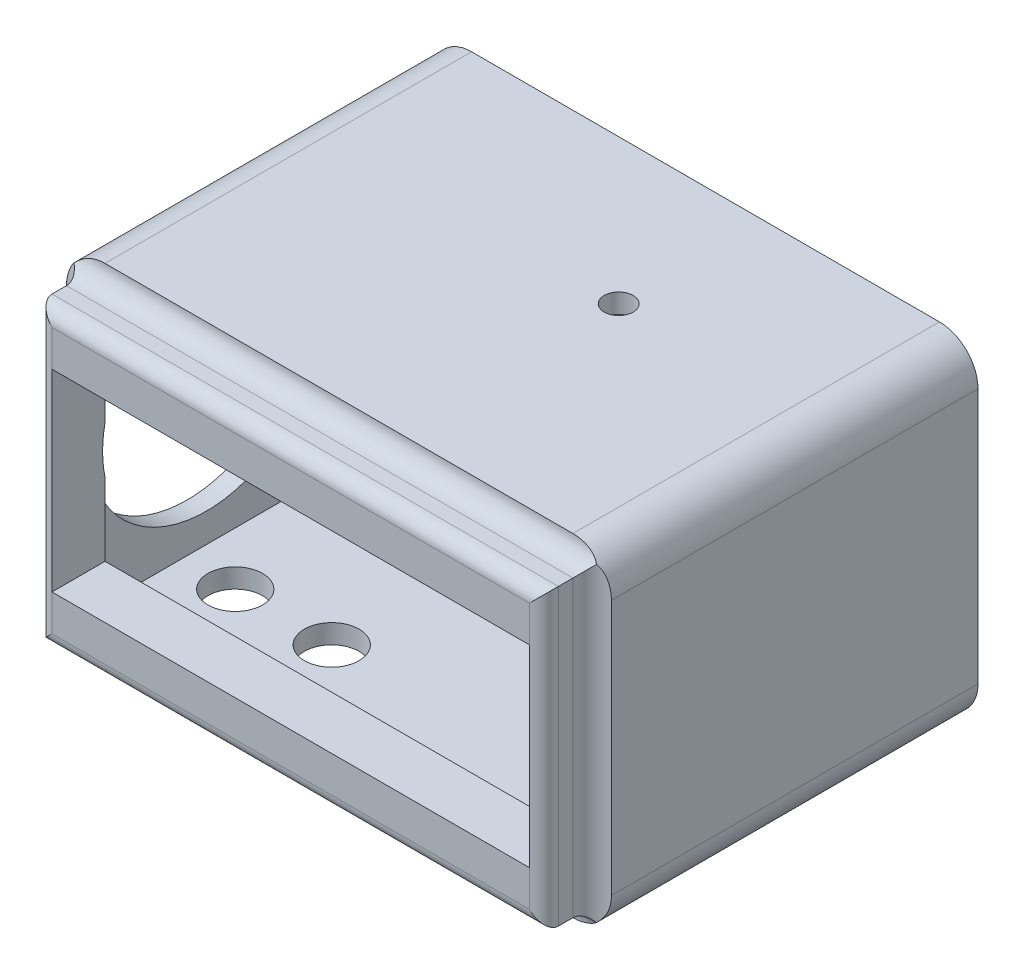
SolidWorks part; units mm, degrees
ref_plane "Ön Düzlem" through (0, 0, 0) normal (0, 0, 1) x (1, 0, 0)
ref_plane "Üst Düzlem" through (0, 0, 0) normal (0, 1, 0) x (1, 0, 0)
ref_plane "Sağ Düzlem" through (0, 0, 0) normal (1, 0, 0) x (0, 0, -1)
sketch "Çizim1" plane through (0, 0, 0) normal (0, 0, 1) x (1, 0, 0)
  line L1 (-49.5, -20) -> (49.5, -20)
  line L2 (-49.5, -20) -> (-49.5, 20)
  line L3 (-49.5, 20) -> (49.5, 20)
  line L4 (49.5, -20) -> (49.5, 20)
  line L5 (-49.5, -20) -> (49.5, 20) construction
  line L6 (-49.5, 20) -> (49.5, -20) construction
  line L7 (-52.5, -30.5) -> (52.5, -30.5)
  line L8 (-52.5, -30.5) -> (-52.5, 30.5)
  line L9 (-52.5, 30.5) -> (52.5, 30.5)
  line L10 (52.5, -30.5) -> (52.5, 30.5)
  line L11 (-52.5, -30.5) -> (52.5, 30.5) construction
  line L12 (-52.5, 30.5) -> (52.5, -30.5) construction
  point P0 (0, 0)
  point P6 (0, 0)
  dimension "D1" = 40
  dimension "D2" = 61
  dimension "D3" = 99
  dimension "D4" = 105
extrude "Yükseklik-Ekstrüzyon1" add sketch "Çizim1" along normal blind 11
sketch "Çizim2" plane through (0, 0, 0) normal (0, 0, -1) x (-1, 0, 0)
  line L1 (52.5, 30.5) -> (-52.5, 30.5)
  line L2 (52.5, 30.5) -> (52.5, -30.5)
  line L3 (52.5, -30.5) -> (-52.5, -30.5)
  line L4 (-52.5, 30.5) -> (-52.5, -30.5)
  line L5 (56.5, 34.5) -> (-56.5, 34.5)
  line L6 (56.5, 34.5) -> (56.5, -34.5)
  line L7 (56.5, -34.5) -> (-56.5, -34.5)
  line L8 (-56.5, 34.5) -> (-56.5, -34.5)
  dimension "D1" = 4
  dimension "D2" = 4
  dimension "D3" = 4
  dimension "D4" = 4
extrude "Yükseklik-Ekstrüzyon2" add sketch "Çizim2" along normal blind 70 separate body
sketch "Çizim3" plane through (0, 0, 0) normal (0, 0, 1) x (1, 0, 0)
  line L1 (-56.5, 34.5) -> (56.5, 34.5)
  line L2 (-56.5, 34.5) -> (-56.5, -34.5)
  line L3 (-56.5, -34.5) -> (56.5, -34.5)
  line L4 (56.5, 34.5) -> (56.5, -34.5)
  line L5 (49.5, -20) -> (-49.5, -20)
  line L6 (49.5, -20) -> (49.5, 20)
  line L7 (49.5, 20) -> (-49.5, 20)
  line L8 (-49.5, -20) -> (-49.5, 20)
extrude "Yükseklik-Ekstrüzyon3" add sketch "Çizim3" along normal blind 1
sketch "Çizim4" plane through (-56.5, 0, 0) normal (-1, 0, 0) x (0, 0, 1)
  line L0 (1, 0) -> (-24, 0) construction
  line L1 (1, 34.5) -> (1, -34.5) construction
  circle A0 centre (-24, 0) radius 24.5
  dimension "D2" = 49
  dimension "D1" = 25
extrude "Kes-Ekstrüzyon1" cut sketch "Çizim4" against normal blind 7
sketch "Çizim5" plane through (0, 34.5, 0) normal (0, 1, 0) x (1, 0, 0)
  line L0 (-56.5, 45) -> (9, 45) construction
  line L1 (-56.5, -1) -> (-56.5, 70) construction
  line L2 (9, 45) -> (15, 45) construction
  line L3 (15, 45) -> (56.5, 45) construction
  line L4 (56.5, -1) -> (56.5, 70) construction
  line L6 (-56.5, 70) -> (56.5, 70) construction
  circle A0 centre (12, 45) radius 3
  dimension "D1" = 6
  dimension "D2" = 65.5
  dimension "D3" = 25
extrude "Kes-Ekstrüzyon2" cut sketch "Çizim5" against normal blind 7
sketch "Çizim6" plane through (0, -34.5, 0) normal (0, -1, 0) x (-1, 0, 0)
  line L0 (56.5, -1) -> (56.5, 70) construction
  line L1 (52.5, -1) -> (-52.5, -1) construction
  line L3 (-56.5, 70) -> (56.5, 70) construction
  line L4 (-38.5, 15) -> (-49.5, 15)
  line L5 (-38.5, 15) -> (-38.5, 25)
  line L6 (-38.5, 25) -> (-49.5, 25)
  line L7 (-49.5, 15) -> (-49.5, 25)
  circle A0 centre (41.5, 19) radius 5.6662
  circle A1 centre (21.5, 19) radius 5.6662
  dimension "D1" = 15
  dimension "D20" = 20
  dimension "D3" = 20
  dimension "D4" = 10
  dimension "D5" = 11
  dimension "D6" = 95
  dimension "D7" = 45
extrude "Kes-Ekstrüzyon3" cut sketch "Çizim6" against normal blind 7
fillet "Radyus1" radius 4 4 edges at (0, -30.5, 1) (52.5, 0, 1) (-52.5, 0, 1) (0, 30.5, 1)
fillet "Radyus2" radius 3 4 edges at (0, -30.5, 11) (52.5, 0, 11) (0, 30.5, 11) (-52.5, 0, 11)
sketch "Çizim7" plane through (0, 0, -70) normal (0, 0, -1) x (-1, 0, 0)
  line L0 (52.5, -30.5) -> (52.5, 30.5) construction
  line L1 (-52.5, 30.5) -> (52.5, 30.5)
  line L2 (-52.5, 30.5) -> (-52.5, 15.5)
  line L3 (-52.5, 15.5) -> (52.5, 15.5)
  line L4 (52.5, 30.5) -> (52.5, 15.5)
  dimension "D1" = 15
sketch "Çizim8" plane through (0, 0, -70) normal (0, 0, -1) x (-1, 0, 0)
  line L0 (-47.5, 24.5) -> (-56.5, 24.5) construction
  line L1 (-47.5, 29.5) -> (47.5, 29.5)
  line L2 (-47.5, 29.5) -> (-47.5, 24.5)
  line L3 (-47.5, 24.5) -> (47.5, 24.5)
  line L4 (47.5, 29.5) -> (47.5, 24.5)
  line L5 (-56.5, 34.5) -> (-56.5, -34.5) construction
  line L6 (47.5, 24.5) -> (56.5, 24.5) construction
  line L7 (56.5, -34.5) -> (56.5, 34.5) construction
  line L8 (56.5, 34.5) -> (-56.5, 34.5) construction
  dimension "D1" = 95
  dimension "D2" = 5
  dimension "D3" = 5
fillet "Radyus4" radius 8 4 edges at (56.5, -34.5, -34.5) (-56.5, -34.5, -34.5) (56.5, 34.5, -34.5) (-56.5, 34.5, -34.5)
sketch "Çizim13" plane through (0, 0, -70) normal (0, 0, -1) x (-1, 0, 0)
  line L0 (-56.5, 26.5) -> (-56.5, -26.5) construction
  line L1 (-48.5, -34.5) -> (48.5, -34.5) construction
  line L2 (56.5, -26.5) -> (56.5, 26.5) construction
  line L3 (48.5, 34.5) -> (-48.5, 34.5) construction
  line L4 (-56.5, 26.5) -> (-56.5, -26.5)
  line L5 (-48.5, -34.5) -> (48.5, -34.5)
  line L6 (56.5, -26.5) -> (56.5, 26.5)
  line L7 (48.5, 34.5) -> (-48.5, 34.5)
  arc A0 (-56.5, -26.5) -> (-48.5, -34.5) centre (-48.5, -26.5) ccw construction
  arc A1 (48.5, -34.5) -> (56.5, -26.5) centre (48.5, -26.5) ccw construction
  arc A2 (56.5, 26.5) -> (48.5, 34.5) centre (48.5, 26.5) ccw construction
  arc A3 (-48.5, 34.5) -> (-56.5, 26.5) centre (-48.5, 26.5) ccw construction
  arc A4 (-56.5, -26.5) -> (-48.5, -34.5) centre (-48.5, -26.5) ccw
  arc A5 (48.5, -34.5) -> (56.5, -26.5) centre (48.5, -26.5) ccw
  arc A6 (56.5, 26.5) -> (48.5, 34.5) centre (48.5, 26.5) ccw
  arc A7 (-48.5, 34.5) -> (-56.5, 26.5) centre (-48.5, 26.5) ccw
sketch "Çizim14" plane through (0, 0, -70) normal (0, 0, -1) x (-1, 0, 0)
  line L1 (-52.5, 30.5) -> (52.5, 30.5)
  line L2 (-52.5, 30.5) -> (-52.5, -30.5)
  line L3 (-52.5, -30.5) -> (52.5, -30.5)
  line L4 (-56.5, 26.5) -> (-56.5, -26.5)
  line L5 (-48.5, -34.5) -> (48.5, -34.5)
  line L6 (56.5, -26.5) -> (56.5, 26.5)
  line L7 (48.5, 34.5) -> (-48.5, 34.5)
  line L8 (-56.5, 26.5) -> (-56.5, -26.5)
  line L9 (-48.5, -34.5) -> (48.5, -34.5)
  line L10 (56.5, -26.5) -> (56.5, 26.5)
  line L11 (48.5, 34.5) -> (-48.5, 34.5)
  line L12 (52.5, 30.5) -> (52.5, -30.5)
  arc A4 (-56.5, -26.5) -> (-48.5, -34.5) centre (-48.5, -26.5) ccw
  arc A5 (48.5, -34.5) -> (56.5, -26.5) centre (48.5, -26.5) ccw
  arc A6 (56.5, 26.5) -> (48.5, 34.5) centre (48.5, 26.5) ccw
  arc A7 (-48.5, 34.5) -> (-56.5, 26.5) centre (-48.5, 26.5) ccw
  arc A8 (-56.5, -26.5) -> (-48.5, -34.5) centre (-48.5, -26.5) ccw
  arc A9 (48.5, -34.5) -> (56.5, -26.5) centre (48.5, -26.5) ccw
  arc A10 (56.5, 26.5) -> (48.5, 34.5) centre (48.5, 26.5) ccw
  arc A11 (-48.5, 34.5) -> (-56.5, 26.5) centre (-48.5, 26.5) ccw
  dimension "D1" = 0
extrude "Yükseklik-Ekstrüzyon8" add sketch "Çizim14" along normal blind 5
sketch "Çizim16" plane through (0, 0, -75) normal (0, 0, -1) x (-1, 0, 0)
  line L0 (-52.5, 30.5) -> (-52.5, -30.5) construction
  line L1 (-52.5, -30.5) -> (52.5, -30.5) construction
  line L2 (52.5, 30.5) -> (-52.5, 30.5) construction
  line L3 (-52.5, 30.5) -> (-52.5, -30.5)
  line L4 (-52.5, -30.5) -> (52.5, -30.5)
  line L5 (52.5, 30.5) -> (-52.5, 30.5)
